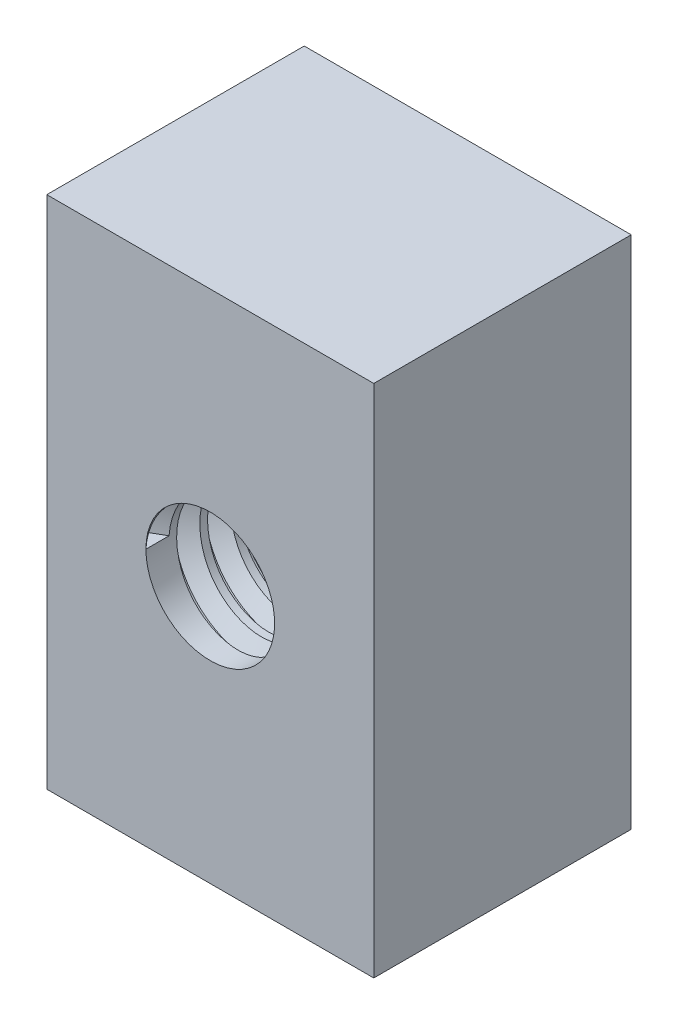
SolidWorks part; units mm, degrees
material "1023 Carbon Steel Sheet (SS)"
ref_plane "Front Plane" through (0, 0, 0) normal (0, 0, 1) x (1, 0, 0)
ref_plane "Top Plane" through (0, 0, 0) normal (0, 1, 0) x (1, 0, 0)
ref_plane "Right Plane" through (0, 0, 0) normal (1, 0, 0) x (0, 0, -1)
sketch "Sketch1" plane through (0, 0, 0) normal (0, 0, 1) x (1, 0, 0)
  line L1 (3.175, -5) -> (-3.175, -5)
  line L2 (3.175, -5) -> (3.175, 5)
  line L3 (3.175, 5) -> (-3.175, 5)
  line L4 (-3.175, -5) -> (-3.175, 5)
  line L5 (3.175, -5) -> (-3.175, 5) construction
  line L6 (3.175, 5) -> (-3.175, -5) construction
  point P0 (0, 0)
  dimension "D1" = 6.35
  dimension "D2" = 10
extrude "Boss-Extrude1" add sketch "Sketch1" along normal blind 5
sketch "Sketch2" plane through (0, 0, 5) normal (0, 0, 1) x (1, 0, 0)
  point P0 (0, 0)
sketch "Sketch3" plane through (0, 0, 5) normal (0, 0, 1) x (1, 0, 0)
  circle A0 centre (0, 0) radius 1.25
  dimension "D1" = 2.5
extrude "Cut-Extrude1" cut sketch "Sketch3" against normal through all
thread "Thread1" pitch 0.6 method cut profile "Thread Profile1" start angle 0, offset 0, length 6, pitch 0.6, diameter 2.5
ref_plane "Plane1" through (-1.25, 0, 5) normal (0, -1, 0) x (-1, 0, 0)
sketch "Thread Profile1" plane through (-1.25, 0, 5) normal (0, -1, 0) x (-1, 0, 0)
  line L0 (0, 0) -> (0, 0.6) construction
  line L1 (0, 0) -> (0.3248, 0.1875)
  line L2 (0.3248, 0.1875) -> (0.3248, 0.2625)
  line L3 (0.3248, 0.2625) -> (0, 0.45)
  line L4 (0.3248, 0.225) -> (0, 0.225) construction
  line L11 (0, 0) -> (0, 0.45)
  point P2 (0, 0)
  dimension "Pitch" = 0.6
  dimension "Profile_Angle" = 60
  dimension "Profile_Land" = 0.075
  dimension "Profile_Height" = 0.3248
